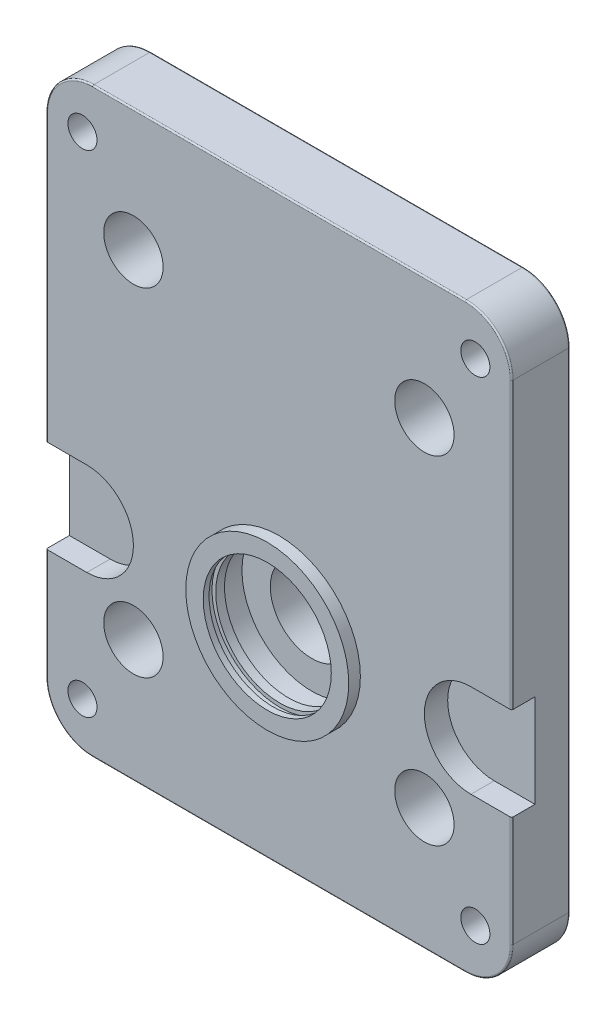
SolidWorks part; units mm, degrees
note: The reader was unsure of these and kept them because the rebuilt part matched: shared geometry of "Sketch1<3>", "Sketch1<4>", "Sketch1<5>", "Sketch1<6>", "Sketch1<8>".
ref_plane "Front Plane" through (0, 0, 0) normal (0, 0, 1) x (1, 0, 0)
ref_plane "Top Plane" through (0, 0, 0) normal (0, 1, 0) x (1, 0, 0)
ref_plane "Right Plane" through (0, 0, 0) normal (1, 0, 0) x (0, 0, -1)
sketch "Sketch1" plane through (0, 0, 0) normal (0, 0, 1) x (1, 0, 0)
  line L0 (0, 0) -> (0, 48.8173) construction
  line L1 (-44.4127, 0) -> (49.5514, 0) construction
  line L2 (15, 45) -> (-15, 45)
  line L3 (-35, 40) -> (-35, 25)
  line L4 (-35, 25) -> (-37, 25)
  line L5 (-37, 25) -> (-37, -25)
  line L6 (35, 25) -> (37, 25)
  line L7 (37, 25) -> (37, -25)
  line L8 (35, 40) -> (35, 25)
  line L9 (35, -40) -> (35, -25)
  line L10 (35, -25) -> (37, -25)
  line L11 (-35, -25) -> (-37, -25)
  line L12 (-35, -40) -> (-35, -25)
  line L13 (15, -45) -> (-15, -45)
  line L14 (-15, -45) -> (-35, -40)
  line L15 (15, -45) -> (35, -40)
  line L16 (15, 45) -> (35, 40)
  line L17 (-15, 45) -> (-35, 40)
  line L18 (0, -15) -> (0, 15) construction
  line L19 (32, 50) -> (-32, 50)
  line L20 (40, 42) -> (40, -42)
  line L21 (32, -50) -> (-32, -50)
  line L22 (-40, 42) -> (-40, -42)
  line L23 (40, 50) -> (-40, -50) construction
  line L24 (40, -50) -> (-40, 50) construction
  line L25 (-20, -15) -> (-20, 15)
  line L26 (20, -15) -> (20, 15)
  line L27 (33, -15) -> (41, -15) construction
  line L28 (33, -7) -> (41, -7)
  line L29 (33, -23) -> (41, -23)
  line L30 (-33, -15) -> (-41, -15) construction
  line L31 (-33, -7) -> (-41, -7)
  line L32 (-33, -23) -> (-41, -23)
  arc A0 (-32, -50) -> (-40, -42) centre (-32, -42) cw
  arc A1 (40, -42) -> (32, -50) centre (32, -42) cw
  arc A2 (32, 50) -> (40, 42) centre (32, 42) cw
  arc A3 (-32, 50) -> (-40, 42) centre (-32, 42) ccw
  arc A4 (-20, -15) -> (20, -15) centre (0, -15) ccw
  arc A5 (20, 15) -> (-20, 15) centre (0, 15) ccw
  arc A6 (33, -7) -> (33, -23) centre (33, -15) ccw
  arc A7 (41, -23) -> (41, -7) centre (41, -15) ccw
  arc A8 (-33, -7) -> (-33, -23) centre (-33, -15) cw
  arc A9 (-41, -23) -> (-41, -7) centre (-41, -15) cw
  circle A10 centre (0, -15) radius 11
  point P6 (-35, 45)
  point P12 (35, -45)
  point P13 (35, 45)
  point P14 (0, 45)
  point P15 (-37, 0)
  point P16 (37, 0)
  point P19 (-35, -45)
  point P20 (0, -45)
  point P29 (25, 29)
  point P30 (25, -29)
  point P31 (-25, -29)
  point P32 (-25, 29)
  point P49 (33.753, 42.1913)
  point P50 (-33.753, 42.1913)
  point P51 (33.753, -42.1913)
  point P52 (-33.753, -42.1913)
  point P55 (0, 0)
  point P62 (37, -15)
  point P70 (-37, -15)
  dimension "D19" = 8
  dimension "D25" = 22
  dimension "D2" = 37
  dimension "D3" = 2
  dimension "D4" = 25
  dimension "D5" = 5
  dimension "D6" = 20
  dimension "D7" = 5
  dimension "D8" = 20
  dimension "D9" = 5
  dimension "D10" = 20
  dimension "D11" = 20
  dimension "D12" = 5
  dimension "D13" = 45
  dimension "D14" = 35
  dimension "D15" = 10
  dimension "D16" = 16
  dimension "D17" = 80
  dimension "D18" = 100
  dimension "D20" = 10
  dimension "D21" = 30
  dimension "D22" = 40
  dimension "D23" = 8
  dimension "D24" = 16
extrude "Boss-Extrude1" add sketch "Sketch1" against normal blind 2 contours L31 A8 L32 L5 L11 L12 L14 L13 L15 L9 L10 L7 L29 A6 L28 L6 L8 L16 L2 L17 L3 L4 A5 L26 A4 L25 | L28 A6 L29 L7 | A8 L31 L5 L32 | L26 A5 L25 A4 A10
extrude "Boss-Extrude2" add sketch "Sketch1<3>" along normal blind 10 contours L19 A3 L22 A0 L21 A1 L20 A2
sketch "Sketch1<3>" plane through (0, 0, 0) normal (0, 0, 1) x (1, 0, 0) same geometry as "Sketch1"
extrude "Cut-Extrude1" cut sketch "Sketch1<4>" against normal blind 4 from surface at 10 contours A9 L31 A8 L32 | A7 L28 A6 L29 starting at face at (0, 0, 10)
sketch "Sketch1<4>" plane through (0, 0, 0) normal (0, 0, 1) x (1, 0, 0) same geometry as "Sketch1"
extrude "Cut-Extrude2" cut sketch "Sketch1<5>" against normal blind 4 from surface at 10 contours A10 starting at face at (0, -7.5, 10)
sketch "Sketch1<5>" plane through (0, 0, 0) normal (0, 0, 1) x (1, 0, 0) same geometry as "Sketch1"
sketch "Sketch2" plane through (0, 0, 10) normal (0, 0, 1) x (1, 0, 0)
  point P0 (0, -15)
hole_wizard "Ø14.25 (14.25) Diameter Hole1" positions "Sketch2" profile "Sketch3" hole size "Ø14.25" standard "ISO" end condition up to next
sketch "Sketch3" plane through (0, -15, 10) normal (1, 0, 0) x (0, -1, 0)
  line L0 (0, 0) -> (0, 12)
  line L1 (0, 12) -> (7.125, 12)
  line L2 (7.125, 12) -> (7.125, 0)
  line L5 (7.125, 0) -> (0, 0)
  line L11 (0, -6.35) -> (0, 107.95) construction
  dimension "Thru Hole Dia." = 14.25
  dimension "Thru Hole Depth" = 12
sketch "Sketch4" plane through (0, 0, 10) normal (0, 0, 1) x (1, 0, 0)
  point P0 (-33.753, 42.1913)
  point P3 (33.753, 42.1913)
  point P6 (33.753, -42.1913)
  point P9 (-33.753, -42.1913)
hole_wizard "Ø5.0 (5) Diameter Hole1" positions "Sketch4" profile "Sketch5" hole size "Ø5.0" standard "ISO"
sketch "Sketch5" plane through (-33.753, 42.1913, 10) normal (1, 0, 0) x (0, -1, 0)
  line L0 (0, 0) -> (0, 10)
  line L1 (0, 10) -> (2.5, 10)
  line L2 (2.5, 10) -> (2.5, 0)
  line L5 (2.5, 0) -> (0, 0)
  line L11 (0, -6.35) -> (0, 107.95) construction
  dimension "Thru Hole Dia." = 5
  dimension "Thru Hole Depth" = 10
sketch "Sketch6" plane through (0, 0, 10) normal (0, 0, 1) x (1, 0, 0)
  point P0 (-25, 29)
  point P3 (25, 29)
  point P6 (25, -29)
  point P9 (-25, -29)
hole_wizard "Ø10.2 (10.2) Diameter Hole1" positions "Sketch6" profile "Sketch7" hole size "Ø10.2" standard "ISO" end condition through all
sketch "Sketch7" plane through (-25, 29, 10) normal (1, 0, 0) x (0, -1, 0)
  line L0 (0, 0) -> (0, 12)
  line L1 (0, 12) -> (5.1, 12)
  line L2 (5.1, 12) -> (5.1, 0)
  line L5 (5.1, 0) -> (0, 0)
  line L11 (0, -6.35) -> (0, 107.95) construction
  dimension "Thru Hole Dia." = 10.2
  dimension "Thru Hole Depth" = 12
extrude "Extrude-Thin1" add sketch "Sketch1<6>" along normal blind 2 from surface at 10 thin contours A10
sketch "Sketch1<6>" plane through (0, 0, 0) normal (0, 0, 1) x (1, 0, 0) same geometry as "Sketch1"
sketch "Sketch8" plane through (0, 0, 0) normal (1, 0, 0) x (0, 0, -1)
  line L0 (0, -15) -> (-12, -15) construction
  line L1 (0, -22.125) -> (0, -7.875) construction
  line L2 (-12, -4) -> (-12, -26) construction
  line L4 (-11, -15) -> (-9.85, -15)
  line L5 (-11, -15) -> (-11, -3.35)
  line L6 (-11, -3.35) -> (-9.85, -3.35)
  line L7 (-9.85, -15) -> (-9.85, -3.35)
  line L8 (-8.35, -15) -> (-4.35, -15)
  line L9 (-8.35, -15) -> (-8.35, -3)
  line L10 (-8.35, -3) -> (-4.35, -3)
  line L11 (-4.35, -15) -> (-4.35, -3)
  dimension "D1" = 11.65
  dimension "D2" = 1.15
  dimension "D3" = 1.5
  dimension "D4" = 4
  dimension "D5" = 12
  dimension "D6" = 1
revolve "Cut-Revolve1" cut sketch "Sketch8" angle 360 about L0
fillet "Fillet1" radius 0.5 8 edges at (37, -25, -1) (35, -25, -1) (37, 25, -1) (35, 25, -1) (-35, -25, -1) (-37, -25, -1) (-37, 25, -1) (-35, 25, -1)
fillet "Fillet2" radius 5 8 edges at (35, 40, -1) (15, 45, -1) (-15, 45, -1) (-35, 40, -1) (-35, -40, -1) (-15, -45, -1) (35, -40, -1) (15, -45, -1)
fillet "Fillet3" radius 0.25 25 edges at (40, -32.5, 10) (37.6569, -47.6569, 10) (-40, -32.5, 10) (-37.6569, -47.6569, 10) (40, 17.5, 10) (37.6569, 47.6569, 10) (-40, 17.5, 10) (-37.6569, 47.6569, 10) (37.6569, 47.6569, 0) (40, 0, 0) (37.6569, -47.6569, 0) (0, -50, 0) (-37.6569, -47.6569, 0) (-40, 0, 0) (-37.6569, 47.6569, 0) (14.9954, 44.9625, 0) (0, 45, 0) (-14.9954, 44.9625, 0) (-23.4049, 42.8988, 0) (-31.443, 40.8834, 0) (0, -50, 10) (0, 50, 10) (0, 50, 0) (23.4049, 42.8988, 0) (31.443, 40.8834, 0)
extrude "Cut-Extrude-Thin1" cut sketch "Sketch1<8>" along normal blind 1 from surface at -2 thin contours A4 L26 A5 L25
sketch "Sketch1<8>" plane through (0, 0, 0) normal (0, 0, 1) x (1, 0, 0) same geometry as "Sketch1"
sketch "Sketch9" plane through (0, 0, -2) normal (0, 0, -1) x (-1, 0, 0)
  point P0 (0, 40)
  point P2 (0, -40)
  dimension "D1" = 40
  dimension "D2" = 80
hole_wizard "Ø3.0 (3) Diameter Hole1" positions "Sketch9" profile "Sketch10" hole size "Ø3.0" standard "ISO"
sketch "Sketch10" plane through (0, 40, -2) normal (1, 0, 0) x (0, 1, 0)
  line L0 (0, 0) -> (0, 2.9013)
  line L1 (0, 2.9013) -> (1.5, 2)
  line L2 (1.5, 2) -> (1.5, 0)
  line L5 (1.5, 0) -> (0, 0)
  line L10 (0, 2.9013) -> (-1.5, 2) construction
  line L11 (0, -6.35) -> (0, 107.95) construction
  dimension "Hole Dia." = 3
  dimension "Hole Depth" = 2
  dimension "Drill Angle" = 118
